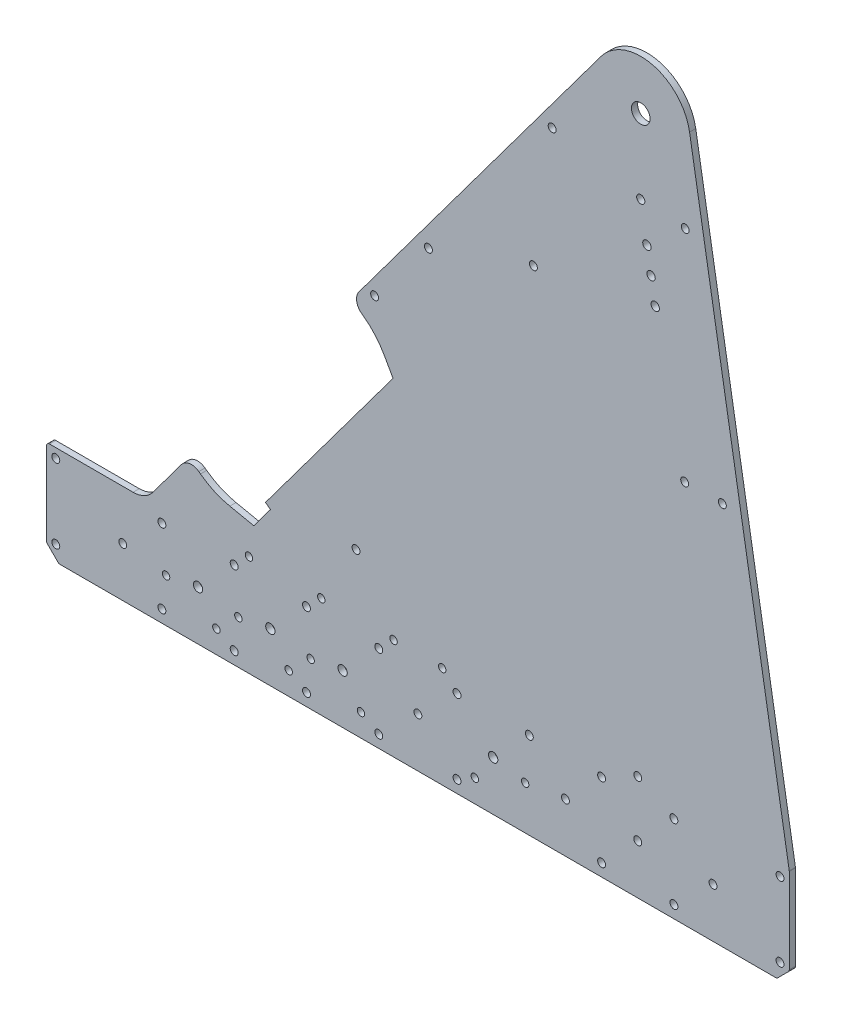
SolidWorks part; units mm, degrees
ref_plane "Front Plane" through (0, 0, 0) normal (0, 0, 1) x (1, 0, 0)
ref_plane "Top Plane" through (0, 0, 0) normal (0, 1, 0) x (1, 0, 0)
ref_plane "Right Plane" through (0, 0, 0) normal (1, 0, 0) x (0, 0, -1)
sketch "Sketch1" plane through (0, 0, 0) normal (0, 0, 1) x (1, 0, 0)
  line L1 (0, 0) -> (381, 0)
  line L2 (0, 0) -> (0, 50.8)
  line L4 (381, 0) -> (381, 50.8)
  line L5 (381, 50.8) -> (329.8448, 353.4827)
  line L6 (0, 50.8) -> (44.4242, 50.8)
  line L7 (54.6089, 55.913) -> (73.025, 80.6347)
  line L9 (112.3289, 80.2488) -> (177.7421, 168.0591)
  line L11 (156.4817, 192.6662) -> (284.4306, 364.4239)
  line L12 (112.3289, 80.2488) -> (114.875, 78.3521)
  line L13 (114.875, 78.3521) -> (106.3397, 66.8943)
  line L14 (156.4817, 192.6662) -> (169.2125, 183.1825)
  line L15 (169.2125, 183.1825) -> (177.7421, 168.0591)
  line L16 (73.025, 80.6347) -> (85.7559, 71.151)
  line L17 (85.7559, 71.151) -> (106.3397, 66.8943)
  line L18 (169.2125, 183.1825) -> (85.7559, 71.151) construction
  arc A0 (284.4306, 364.4239) -> (329.8448, 353.4827) centre (304.8, 349.25) cw
  arc A1 (44.4242, 50.8) -> (54.6089, 55.913) centre (44.4242, 63.5) ccw
  point P11 (50.8, 50.8)
  dimension "D4" = 349.25
  dimension "D7" = 12.7
  dimension "D5" = 25.4
  dimension "D1" = 50.8
  dimension "D2" = 381
  dimension "D3" = 76.2
  dimension "D6" = 50.8
  dimension "D8" = 123.825
  dimension "D9" = 139.7
  dimension "D10" = 15.875
  dimension "D11" = 31.75
  dimension "D12" = 73.025
  dimension "D13" = 3.175
  dimension "D14" = 14.2875
  dimension "D15" = 115
extrude "Boss-Extrude1" add sketch "Sketch1" along normal blind 3.175
sketch "Sketch2" plane through (0, 0, 3.175) normal (0, 0, 1) x (1, 0, 0)
  line L1 (190.5, 50.8) -> (190.5, 0) construction
  line L3 (0, 0) -> (381, 0) construction
  line L5 (0, 6.35) -> (0, 0)
  line L6 (0, 50.8) -> (0, 0) construction
  line L7 (0, 0) -> (6.35, 0)
  line L8 (6.35, 0) -> (0, 6.35)
  line L9 (381, 0) -> (374.65, 0)
  line L10 (374.65, 0) -> (381, 6.35)
  line L11 (381, 6.35) -> (381, 0)
  circle A19 centre (4.7625, 46.0375) radius 2.032
  circle A20 centre (4.7625, 7.9375) radius 2.032
  circle A21 centre (376.2375, 7.9375) radius 2.032
  circle A22 centre (376.2375, 46.0375) radius 2.032
  dimension "D21" = 6.35
  dimension "D27" = 4.064
  dimension "D4" = 46.0375
  dimension "D22" = 6.35
  dimension "D25" = 4.7625
  dimension "D28" = 7.9375
extrude "Cut-Extrude1" cut sketch "Sketch2" against normal up to next
sketch "Sketch5" plane through (0, 0, 3.175) normal (0, 0, 1) x (1, 0, 0)
  line L0 (151.892, 25.4) -> (229.108, 25.4) construction
  line L1 (229.108, 25.4) -> (341.884, 25.4) construction
  circle A0 centre (39.116, 25.4) radius 2.032
  circle A1 centre (59.182, 6.35) radius 2.032
  circle A2 centre (59.182, 44.45) radius 2.032
  circle A3 centre (96.266, 44.45) radius 2.032
  circle A4 centre (133.35, 44.45) radius 2.032
  circle A5 centre (170.434, 44.45) radius 2.032
  circle A6 centre (210.566, 44.45) radius 2.032
  circle A7 centre (210.566, 6.35) radius 2.032
  circle A8 centre (170.434, 6.35) radius 2.032
  circle A9 centre (247.65, 44.45) radius 2.032
  circle A10 centre (266.192, 25.4) radius 2.032
  circle A11 centre (39.116, 25.4) radius 2.286 construction
  circle A12 centre (59.182, 44.45) radius 1.905 construction
  circle A13 centre (59.182, 6.35) radius 1.905 construction
  circle A14 centre (96.266, 44.45) radius 1.905 construction
  circle A15 centre (133.35, 44.45) radius 1.905 construction
  circle A16 centre (170.434, 44.45) radius 1.905 construction
  circle A17 centre (170.434, 6.35) radius 2.159 construction
  circle A18 centre (210.566, 6.35) radius 2.159 construction
  circle A19 centre (210.566, 44.45) radius 1.905 construction
  circle A20 centre (247.65, 44.45) radius 1.905 construction
  circle A21 centre (266.192, 25.4) radius 1.905 construction
  circle A22 centre (77.724, 25.4) radius 2.3813
  circle A23 centre (114.808, 25.4) radius 2.3813
  circle A24 centre (151.892, 25.4) radius 2.3813
  circle A25 centre (229.108, 25.4) radius 2.3813
  circle A26 centre (190.5, 25.4) radius 2.032
  circle A28 centre (303.276, 25.4) radius 2.032
  circle A29 centre (341.884, 25.4) radius 2.032
  circle A30 centre (77.724, 25.4) radius 7.366 construction
  circle A31 centre (114.808, 25.4) radius 7.366 construction
  circle A32 centre (151.892, 25.4) radius 7.366 construction
  circle A33 centre (229.108, 25.4) radius 7.366 construction
  dimension "D1" = 4.064
  dimension "D2" = 4.7625
  dimension "D3" = 37.084
  dimension "D4" = 38.608
  dimension "D5" = 38.608
extrude "Cut-Extrude4" cut sketch "Sketch5" against normal through all
sketch "Sketch6" plane through (0, 0, 3.175) normal (0, 0, 1) x (1, 0, 0)
  line L0 (6.35, 0) -> (374.65, 0) construction
  line L1 (266.192, 25.4) -> (303.276, 25.4) construction
  line L2 (284.734, 6.35) -> (284.734, 44.45) construction
  line L3 (151.892, 25.4) -> (114.808, 25.4) construction
  line L4 (114.808, 25.4) -> (77.724, 25.4) construction
  circle A0 centre (284.734, 44.45) radius 2.032
  circle A1 centre (284.734, 6.35) radius 2.032
  circle A2 centre (321.818, 6.35) radius 2.032
  circle A3 centre (321.818, 44.45) radius 2.032
  circle A4 centre (96.266, 6.35) radius 2.032
  circle A5 centre (133.35, 6.35) radius 2.032
  circle A6 centre (303.276, 53.975) radius 2.032
  arc A7 (304.329, 52.3875) -> (302.223, 52.3875) centre (303.276, 53.975) ccw construction
  point P8 (284.734, 25.4)
  point P9 (284.734, 25.4)
  point P28 (96.266, 25.4)
  point P30 (133.35, 25.4)
  dimension "D1" = 4.064
  dimension "D2" = 6.35
  dimension "D3" = 37.084
extrude "Cut-Extrude5" cut sketch "Sketch6" against normal through all
sketch "Sketch3" plane through (0, 0, 3.175) normal (0, 0, 1) x (1, 0, 0)
  line L0 (73.025, 80.6347) -> (54.6089, 55.913) construction
  line L1 (381, 6.35) -> (381, 50.8) construction
  line L2 (6.35, 0) -> (374.65, 0) construction
  line L3 (304.8, 349.25) -> (304.8, 311.15) construction
  line L4 (307.9745, 292.3664) -> (304.8, 311.15) construction
  line L5 (307.9745, 292.3664) -> (310.0909, 279.8439) construction
  line L6 (310.0909, 279.8439) -> (312.2073, 267.3215) construction
  line L7 (381, 50.8) -> (329.8448, 353.4827) construction
  line L8 (73.025, 80.6347) -> (54.6089, 55.913) construction
  line L9 (0, 50.8) -> (0, 6.35) construction
  circle A0 centre (304.8, 349.25) radius 4.7625
  circle A1 centre (168.275, 200.025) radius 2.032
  circle A2 centre (158.75, 82.55) radius 2.032
  circle A3 centre (304.8, 311.15) radius 2.0955
  circle A5 centre (307.9745, 292.3664) radius 2.159
  circle A6 centre (310.0909, 279.8439) radius 2.159
  circle A7 centre (312.2073, 267.3215) radius 2.159
  circle A8 centre (327.6094, 309.5518) radius 2.032
  circle A9 centre (346.6566, 196.85) radius 2.032
  circle A10 centre (195.8987, 234.95) radius 2.032
  circle A11 centre (249.7483, 254.0902) radius 2.032
  circle A12 centre (259.3534, 320.1311) radius 2.032
  circle A13 centre (327.3365, 196.85) radius 2.032
  dimension "D1" = 9.525
  dimension "D3" = 4.064
  dimension "D6" = 4.064
  dimension "D11" = 4.318
  dimension "D10" = 4.191
  dimension "D13" = 4.064
  dimension "D20" = 4.064
  dimension "D4" = 222.25
  dimension "D5" = 82.55
  dimension "D7" = 19.05
  dimension "D8" = 12.7
  dimension "D9" = 38.1
  dimension "D12" = 12.7
  dimension "D14" = 9.525
  dimension "D15" = 9.525
  dimension "D16" = 114.3
  dimension "D17" = 196.85
  dimension "D18" = 6.35
  dimension "D19" = 234.95
  dimension "D21" = 57.15
  dimension "D22" = 38.1
  dimension "D23" = 53.975
  dimension "D24" = 6.35
  dimension "D25" = 200.025
  dimension "D26" = 168.275
  dimension "D27" = 28.575
extrude "Cut-Extrude2" cut sketch "Sketch3" against normal through all
fillet "Fillet1" radius 1.5875 6 edges at (374.65, 0, 1.5875) (381, 6.35, 1.5875) (381, 50.8, 1.5875) (6.35, 0, 1.5875) (0, 6.35, 1.5875) (0, 50.8, 1.5875)
sketch "Sketch4" plane through (0, 0, 0) normal (0, 0, -1) x (-1, 0, 0)
  circle A0 centre (-61.3181, 22.2981) radius 1.905 construction
  circle A1 centre (-87.1313, 11.606) radius 1.905 construction
  circle A2 centre (-98.4021, 22.2981) radius 1.905 construction
  circle A3 centre (-124.2153, 11.606) radius 1.905 construction
  circle A4 centre (-135.4861, 22.2981) radius 1.905 construction
  circle A5 centre (-161.2993, 11.606) radius 1.905 construction
  circle A6 centre (-245.5139, 22.2981) radius 1.905 construction
  circle A7 centre (-219.7007, 11.606) radius 1.905 construction
  circle A8 centre (-202.982, 51.9684) radius 1.905 construction
  circle A9 centre (-178.018, 51.9684) radius 1.905 construction
  circle A10 centre (-140.934, 51.9684) radius 1.905 construction
  circle A11 centre (-103.85, 51.9684) radius 1.905 construction
  circle A12 centre (-61.3181, 22.2981) radius 1.905
  circle A13 centre (-87.1313, 11.606) radius 1.905
  circle A14 centre (-98.4021, 22.2981) radius 1.905
  circle A15 centre (-124.2153, 11.606) radius 1.905
  circle A16 centre (-135.4861, 22.2981) radius 1.905
  circle A17 centre (-161.2993, 11.606) radius 1.905
  circle A18 centre (-245.5139, 22.2981) radius 1.905
  circle A19 centre (-219.7007, 11.606) radius 1.905
  circle A20 centre (-202.982, 51.9684) radius 1.905
  circle A21 centre (-178.018, 51.9684) radius 1.905
  circle A22 centre (-140.934, 51.9684) radius 1.905
  circle A23 centre (-103.85, 51.9684) radius 1.905
extrude "Cut-Extrude3" cut sketch "Sketch4" against normal up to next
fillet "Fillet2" radius 38.1 2 edges at (85.7559, 71.151, 1.5875) (169.2125, 183.1825, 1.5875)
fillet "Fillet3" radius 6.35 2 edges at (73.025, 80.6347, 1.5875) (156.4817, 192.6662, 1.5875)
